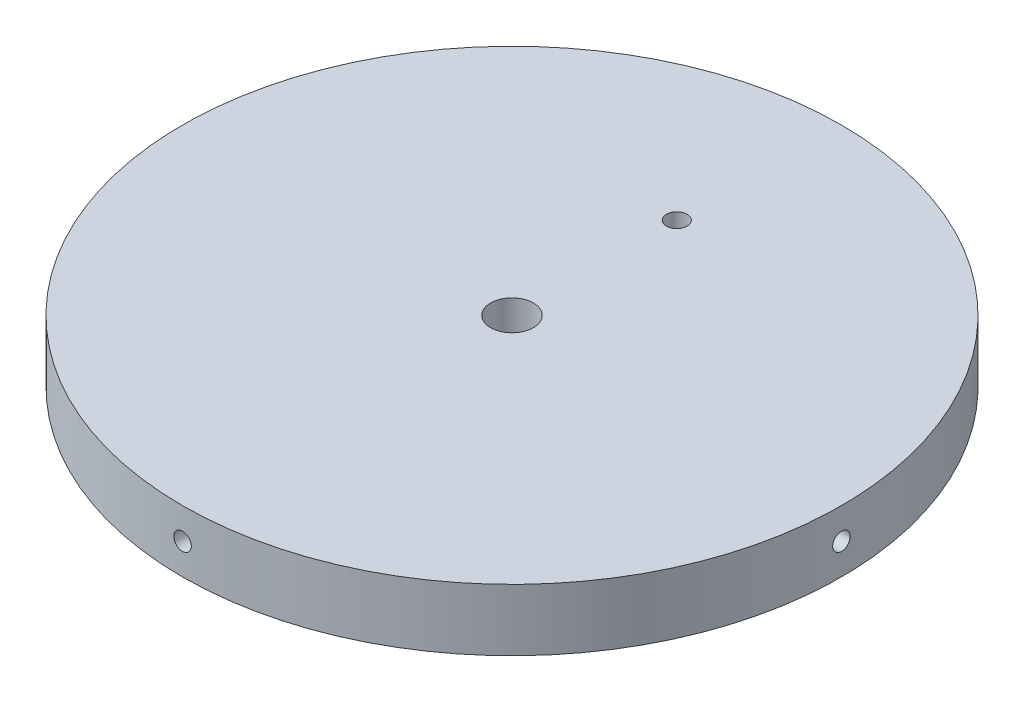
SolidWorks part; units mm, degrees
ref_plane "Front Plane" through (0, 0, 0) normal (0, 0, 1) x (1, 0, 0)
ref_plane "Top Plane" through (0, 0, 0) normal (0, 1, 0) x (1, 0, 0)
ref_plane "Right Plane" through (0, 0, 0) normal (1, 0, 0) x (0, 0, -1)
sketch "Sketch1" plane through (0, 0, 0) normal (0, 1, 0) x (1, 0, 0)
  circle A0 centre (0, 0) radius 50.8
  circle A1 centre (0, 0) radius 3.3
  circle A2 centre (0, 25.4) radius 1.5875
  dimension "D1" = 101.6
  dimension "D2" = 6.6
  dimension "D3" = 3.175
  dimension "D4" = 25.4
extrude "Boss-Extrude1" add sketch "Sketch1" along normal mid plane 9.525
ref_plane "Plane1" through (0, 0, 50.8) normal (0, 0, 1) x (1, 0, 0)
sketch "Sketch2" plane through (0, 0, 50.8) normal (0, 0, 1) x (1, 0, 0)
  circle A0 centre (0, 0) radius 1.3526
  dimension "D1" = 2.7051
extrude "Cut-Extrude1" cut sketch "Sketch2" against normal blind 12.7
sketch "Sketch3" plane through (0, 0, 0) normal (0, 0, 1) x (1, 0, 0)
  line L0 (0, 4.7625) -> (0, -4.7625)
  line L1 (50.8, 4.7625) -> (-50.8, 4.7625) construction
  line L2 (-50.8, -4.7625) -> (50.8, -4.7625) construction
pattern_circular "CirPattern1" count 4 over 360 about axis through (0, 4.7625, 0) along (0, -1, 0) of "Cut-Extrude1"
